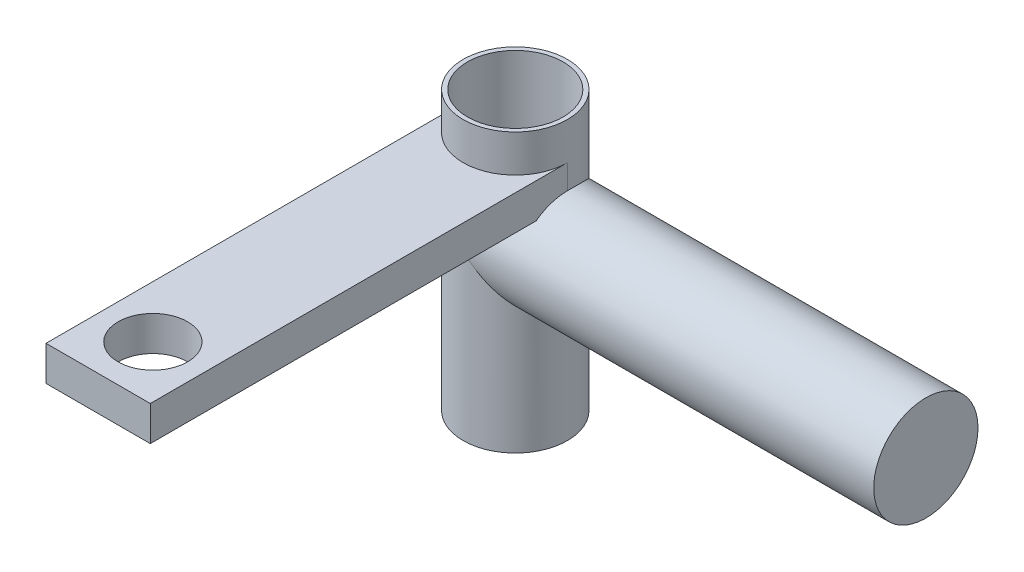
SolidWorks part; units mm, degrees
ref_plane "Front Plane" through (0, 0, 0) normal (0, 0, 1) x (1, 0, 0)
ref_plane "Top Plane" through (0, 0, 0) normal (0, 1, 0) x (1, 0, 0)
ref_plane "Right Plane" through (0, 0, 0) normal (1, 0, 0) x (0, 0, -1)
sketch "Sketch1" plane through (0, 0, 0) normal (0, 1, 0) x (1, 0, 0)
  circle A0 centre (0, 0) radius 9.525
  dimension "D1" = 19.05
extrude "Sleeve" add sketch "Sketch1" along normal blind 50.8
sketch "Sketch2" plane through (0, 0, 0) normal (0, 0, 1) x (1, 0, 0)
  line L0 (0, -10.4775) -> (0, 10.4775) construction
  line L1 (9.525, 43.975) -> (-9.525, 43.975)
  line L2 (9.525, 43.975) -> (9.525, 37.625)
  line L3 (9.525, 37.625) -> (-9.525, 37.625)
  line L4 (-9.525, 43.975) -> (-9.525, 37.625)
  line L5 (9.525, 43.975) -> (-9.525, 37.625) construction
  line L6 (9.525, 37.625) -> (-9.525, 43.975) construction
  point P0 (0, 40.8)
  dimension "D1" = 6.35
  dimension "D2" = 19.05
  dimension "D3" = 40.8
extrude "Bracket" add sketch "Sketch2" along normal blind 76.2
sketch "Sketch4" plane through (0, 0, 0) normal (0, 1, 0) x (1, 0, 0)
  line L0 (0, -27.94) -> (0, 27.94) construction
  circle A0 centre (0, -66.2) radius 6.35
  dimension "D1" = 12.7
  dimension "D2" = 66.2
extrude "Bracket Hole" cut sketch "Sketch4" along normal through all
sketch "Sketch5" plane through (0, 0, 0) normal (1, 0, 0) x (0, 0, -1)
  line L0 (0, 10.4775) -> (0, -10.4775) construction
  circle A0 centre (0, 30) radius 9.525
  dimension "D2" = 19.05
  dimension "D1" = 30
extrude "Shaft" add sketch "Sketch5" along normal blind 75
sketch "Sketch6" plane through (0, 0, 0) normal (0, 1, 0) x (1, 0, 0)
  circle A0 centre (0, 0) radius 8.7313
  dimension "D1" = 17.4625
extrude "Sleeve Hole" cut sketch "Sketch6" along normal through all
equation "\"shaftDiameter\"= 25.4 / 4 * 3mm"
equation "\"shaftLength\"= 75mm"
equation "\"sleeveDiameter\"= 25.4 / 4 * 3mm"
equation "\"sleeveLength\"= 2 * 25.4mm"
equation "\"bracketLength\"= 3 * 25.4mm"
equation "\"D1@Sketch1\"=\"sleeveDiameter\""
equation "\"D1@Sleeve\" = \"sleeveLength\""
equation "\"D3@Sketch2\"=\"sleeveLength\"-10"
equation "\"D1@Bracket\" = \"bracketLength\""
equation "\"tieBarHoleDiameter\"= 25.4 / 2mm"
equation "\"D1@Sketch4\"=\"tieBarHoleDiameter\""
equation "\"D2@Sketch4\"=\"bracketLength\"-10"
equation "\"D2@Sketch5\"=\"shaftDiameter\""
equation "\"D1@Shaft\" = \"shaftLength\""
equation "\"sleeveWallThickness\"= 25.4 / 16"
equation "\"D1@Sketch6\"=\"sleeveDiameter\"-\"sleeveWallThickness\""
